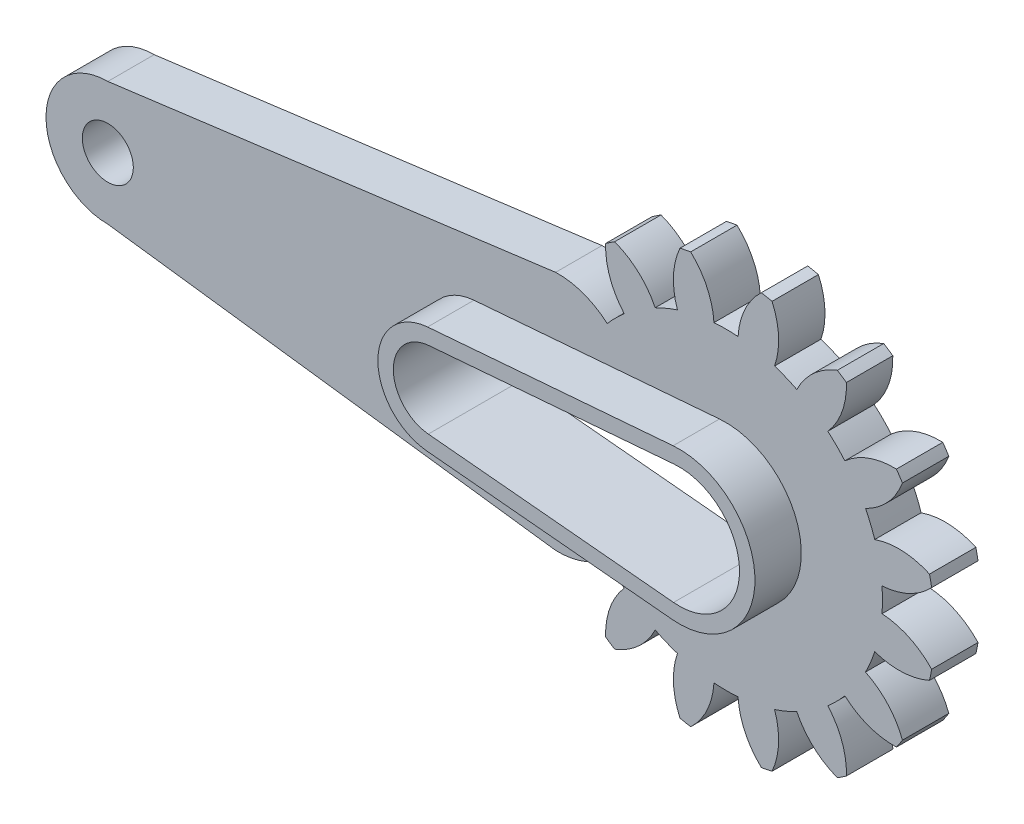
SolidWorks part; units mm, degrees
ref_plane "Front Plane" through (0, 0, 0) normal (0, 0, 1) x (1, 0, 0)
ref_plane "Top Plane" through (0, 0, 0) normal (0, 1, 0) x (1, 0, 0)
ref_plane "Right Plane" through (0, 0, 0) normal (1, 0, 0) x (0, 0, -1)
sketch "Sketch1" plane through (0, 0, 0) normal (0, 0, 1) x (1, 0, 0)
  line L0 (2.5866, 4.9713) -> (-37.4134, 4.9713) construction
  line L7 (2.2444, 8.8475) -> (-13.6422, 7.5599)
  line L8 (-13.6757, 2.5792) -> (2.192, 1.0776)
  line L9 (2.2848, 8.3491) -> (-13.6018, 7.0615)
  line L10 (-13.6286, 3.077) -> (2.2391, 1.5753)
  line L13 (2.1636, 9.8442) -> (-13.723, 8.5566)
  line L14 (-13.77, 1.5836) -> (2.0978, 0.082)
  line L15 (-37.4134, 8.9713) -> (-8.4386, 12.7621)
  line L16 (-37.4134, 0.9713) -> (-8.4386, -2.8194)
  circle A1 centre (2.5866, 4.9713) radius 1.5
  circle A2 centre (2.5866, 4.9713) radius 1.5
  arc A3 (-37.4134, 8.9713) -> (-37.4134, 0.9713) centre (-37.4134, 4.9713) ccw
  circle A4 centre (2.5866, 4.9713) radius 1.5224
  circle A5 centre (2.5866, 4.9713) radius 1.5
  circle A6 centre (2.5866, 4.9713) radius 1.65
  circle A7 centre (-37.4134, 4.9713) radius 1.65
  arc A8 (2.192, 1.0776) -> (2.2444, 8.8475) centre (2.5594, 4.9602) ccw
  arc A9 (-0.8405, 4.9831) -> (2.2391, 1.5753) centre (2.5594, 4.9602) ccw construction
  arc A13 (-0.8405, 4.9831) -> (-0.8406, 4.9713) centre (2.5594, 4.9602) ccw
  arc A16 (-13.6422, 7.5599) -> (-13.6757, 2.5792) centre (-13.4402, 5.0681) ccw
  arc A18 (-0.8405, 4.9831) -> (2.2391, 1.5753) centre (2.5594, 4.9602) ccw
  arc A19 (2.2848, 8.3491) -> (-0.8405, 4.9831) centre (2.5594, 4.9602) ccw
  arc A20 (-13.6018, 7.0615) -> (-13.6286, 3.077) centre (-13.4402, 5.0681) ccw
  arc A21 (-0.8405, 4.9831) -> (-0.8406, 4.9713) centre (2.5594, 4.9602) ccw
  arc A24 (-13.723, 8.5566) -> (-13.77, 1.5836) centre (-13.4402, 5.0681) ccw
  arc A25 (2.0978, 0.082) -> (2.1636, 9.8442) centre (2.5594, 4.9602) ccw
  circle A31 centre (2.5594, 4.9602) radius 3.4
  arc A32 (-0.8405, 4.9831) -> (-0.8406, 4.9713) centre (2.5594, 4.9602) ccw
  arc A66 (12.6806, 5.7512) -> (15.8915, 7.2585) centre (12.3907, 10.5424) ccw
  arc A67 (15.8915, 7.2585) -> (15.754, 7.9499) centre (2.5866, 4.9713) ccw
  arc A68 (15.754, 7.9499) -> (12.2106, 8.1137) centre (13.7763, 3.5762) ccw
  arc A69 (12.2106, 8.1137) -> (11.6138, 9.5546) centre (2.5866, 4.9713) ccw
  arc A70 (11.6138, 9.5546) -> (14.0035, 12.1759) centre (9.5124, 13.8702) ccw
  arc A71 (14.0035, 12.1759) -> (13.6118, 12.7621) centre (2.5866, 4.9713) ccw
  arc A72 (13.6118, 12.7621) -> (10.2755, 11.5574) centre (13.4584, 7.9645) ccw
  arc A73 (10.2755, 11.5574) -> (9.1727, 12.6602) centre (2.5866, 4.9713) ccw
  arc A74 (9.1727, 12.6602) -> (10.3773, 15.9965) centre (5.5798, 15.8432) ccw
  arc A75 (10.3773, 15.9965) -> (9.7912, 16.3882) centre (2.5866, 4.9713) ccw
  arc A76 (9.7912, 16.3882) -> (7.1699, 13.9985) centre (11.4854, 11.8971) ccw
  arc A77 (7.1699, 13.9985) -> (5.729, 14.5953) centre (2.5866, 4.9713) ccw
  arc A78 (5.729, 14.5953) -> (5.5652, 18.1387) centre (1.1915, 16.161) ccw
  arc A79 (5.5652, 18.1387) -> (4.8738, 18.2762) centre (2.5866, 4.9713) ccw
  arc A80 (4.8738, 18.2762) -> (3.3664, 15.0653) centre (8.1577, 14.7754) ccw
  arc A81 (3.3664, 15.0653) -> (1.8068, 15.0653) centre (2.5866, 4.9713) ccw
  arc A82 (1.8068, 15.0653) -> (0.2995, 18.2762) centre (-2.9844, 14.7754) ccw
  arc A83 (0.2995, 18.2762) -> (-0.3919, 18.1387) centre (2.5866, 4.9713) ccw
  arc A84 (-0.3919, 18.1387) -> (-0.5557, 14.5953) centre (3.9818, 16.161) ccw
  arc A85 (-0.5557, 14.5953) -> (-1.9966, 13.9985) centre (2.5866, 4.9713) ccw
  arc A86 (-1.9966, 13.9985) -> (-4.6179, 16.3882) centre (-6.3122, 11.8971) ccw
  arc A87 (-4.6179, 16.3882) -> (-5.2041, 15.9965) centre (2.5866, 4.9713) ccw
  arc A88 (-5.2041, 15.9965) -> (-3.9994, 12.6602) centre (-0.4065, 15.8432) ccw
  arc A89 (-3.9994, 12.6602) -> (-5.1022, 11.5574) centre (2.5866, 4.9713) ccw
  arc A90 (-5.1022, 11.5574) -> (-8.4386, 12.7621) centre (-8.2852, 7.9645) ccw
  arc A91 (-8.4386, 12.7621) -> (-8.8302, 12.1759) centre (2.5866, 4.9713) ccw
  arc A92 (-8.8302, 12.1759) -> (-6.4405, 9.5546) centre (-4.3391, 13.8702) ccw
  arc A93 (-6.4405, 9.5546) -> (-7.0373, 8.1137) centre (2.5866, 4.9713) ccw
  arc A94 (-7.0373, 8.1137) -> (-10.5807, 7.9499) centre (-8.603, 3.5762) ccw
  arc A95 (-10.5807, 7.9499) -> (-10.7182, 7.2585) centre (2.5866, 4.9713) ccw
  arc A96 (-10.7182, 7.2585) -> (-7.5073, 5.7512) centre (-7.2174, 10.5424) ccw
  arc A97 (-7.5073, 5.7512) -> (-7.5073, 4.1915) centre (2.5866, 4.9713) ccw
  arc A98 (-7.5073, 4.1915) -> (-10.7182, 2.6842) centre (-7.2174, -0.5997) ccw
  arc A99 (-10.7182, 2.6842) -> (-10.5807, 1.9928) centre (2.5866, 4.9713) ccw
  arc A100 (-10.5807, 1.9928) -> (-7.0373, 1.829) centre (-8.603, 6.3665) ccw
  arc A101 (-7.0373, 1.829) -> (-6.4405, 0.3881) centre (2.5866, 4.9713) ccw
  arc A102 (-6.4405, 0.3881) -> (-8.8302, -2.2332) centre (-4.3391, -3.9275) ccw
  arc A103 (-8.8302, -2.2332) -> (-8.4386, -2.8194) centre (2.5866, 4.9713) ccw
  arc A104 (-8.4386, -2.8194) -> (-5.1022, -1.6147) centre (-8.2852, 1.9782) ccw
  arc A105 (-5.1022, -1.6147) -> (-3.9994, -2.7175) centre (2.5866, 4.9713) ccw
  arc A106 (-3.9994, -2.7175) -> (-5.2041, -6.0538) centre (-0.4065, -5.9005) ccw
  arc A107 (-5.2041, -6.0538) -> (-4.6179, -6.4455) centre (2.5866, 4.9713) ccw
  arc A108 (-4.6179, -6.4455) -> (-1.9966, -4.0558) centre (-6.3122, -1.9544) ccw
  arc A109 (-1.9966, -4.0558) -> (-0.5557, -4.6526) centre (2.5866, 4.9713) ccw
  arc A110 (-0.5557, -4.6526) -> (-0.3919, -8.196) centre (3.9818, -6.2183) ccw
  arc A111 (-0.3919, -8.196) -> (0.2995, -8.3335) centre (2.5866, 4.9713) ccw
  arc A112 (0.2995, -8.3335) -> (1.8068, -5.1226) centre (-2.9844, -4.8327) ccw
  arc A113 (1.8068, -5.1226) -> (3.3664, -5.1226) centre (2.5866, 4.9713) ccw
  arc A114 (3.3664, -5.1226) -> (4.8738, -8.3335) centre (8.1577, -4.8327) ccw
  arc A115 (4.8738, -8.3335) -> (5.5652, -8.196) centre (2.5866, 4.9713) ccw
  arc A116 (5.5652, -8.196) -> (5.729, -4.6526) centre (1.1915, -6.2183) ccw
  arc A117 (5.729, -4.6526) -> (7.1699, -4.0558) centre (2.5866, 4.9713) ccw
  arc A118 (7.1699, -4.0558) -> (9.7912, -6.4455) centre (11.4854, -1.9544) ccw
  arc A119 (9.7912, -6.4455) -> (10.3773, -6.0538) centre (2.5866, 4.9713) ccw
  arc A120 (10.3773, -6.0538) -> (9.1727, -2.7175) centre (5.5798, -5.9005) ccw
  arc A121 (9.1727, -2.7175) -> (10.2755, -1.6147) centre (2.5866, 4.9713) ccw
  arc A122 (10.2755, -1.6147) -> (13.6118, -2.8194) centre (13.4584, 1.9782) ccw
  arc A123 (13.6118, -2.8194) -> (14.0035, -2.2332) centre (2.5866, 4.9713) ccw
  arc A124 (14.0035, -2.2332) -> (11.6138, 0.3881) centre (9.5124, -3.9275) ccw
  arc A125 (11.6138, 0.3881) -> (12.2106, 1.829) centre (2.5866, 4.9713) ccw
  arc A126 (12.2106, 1.829) -> (15.754, 1.9928) centre (13.7763, 6.3665) ccw
  arc A127 (15.754, 1.9928) -> (15.8915, 2.6842) centre (2.5866, 4.9713) ccw
  arc A128 (15.8915, 2.6842) -> (12.6806, 4.1915) centre (12.3907, -0.5997) ccw
  arc A129 (12.6806, 4.1915) -> (12.6806, 5.7512) centre (2.5866, 4.9713) ccw
  arc A130 (12.6806, 5.7512) -> (15.8915, 7.2585) centre (12.3907, 10.5424) ccw
  arc A131 (15.8915, 7.2585) -> (15.754, 7.9499) centre (2.5866, 4.9713) ccw
  arc A132 (15.754, 7.9499) -> (12.2106, 8.1137) centre (13.7763, 3.5762) ccw
  arc A133 (12.2106, 8.1137) -> (11.6138, 9.5546) centre (2.5866, 4.9713) ccw
  arc A134 (11.6138, 9.5546) -> (14.0035, 12.1759) centre (9.5124, 13.8702) ccw
  arc A135 (14.0035, 12.1759) -> (13.6118, 12.7621) centre (2.5866, 4.9713) ccw
  arc A136 (13.6118, 12.7621) -> (10.2755, 11.5574) centre (13.4584, 7.9645) ccw
  arc A137 (10.2755, 11.5574) -> (9.1727, 12.6602) centre (2.5866, 4.9713) ccw
  arc A138 (9.1727, 12.6602) -> (10.3773, 15.9965) centre (5.5798, 15.8432) ccw
  arc A139 (10.3773, 15.9965) -> (9.7912, 16.3882) centre (2.5866, 4.9713) ccw
  arc A140 (9.7912, 16.3882) -> (7.1699, 13.9985) centre (11.4854, 11.8971) ccw
  arc A141 (7.1699, 13.9985) -> (5.729, 14.5953) centre (2.5866, 4.9713) ccw
  arc A142 (5.729, 14.5953) -> (5.5652, 18.1387) centre (1.1915, 16.161) ccw
  arc A143 (5.5652, 18.1387) -> (4.8738, 18.2762) centre (2.5866, 4.9713) ccw
  arc A144 (4.8738, 18.2762) -> (3.3664, 15.0653) centre (8.1577, 14.7754) ccw
  arc A145 (3.3664, 15.0653) -> (1.8068, 15.0653) centre (2.5866, 4.9713) ccw
  arc A146 (1.8068, 15.0653) -> (0.2995, 18.2762) centre (-2.9844, 14.7754) ccw
  arc A147 (0.2995, 18.2762) -> (-0.3919, 18.1387) centre (2.5866, 4.9713) ccw
  arc A148 (-0.3919, 18.1387) -> (-0.5557, 14.5953) centre (3.9818, 16.161) ccw
  arc A149 (-0.5557, 14.5953) -> (-1.9966, 13.9985) centre (2.5866, 4.9713) ccw
  arc A150 (-1.9966, 13.9985) -> (-4.6179, 16.3882) centre (-6.3122, 11.8971) ccw
  arc A151 (-4.6179, 16.3882) -> (-5.2041, 15.9965) centre (2.5866, 4.9713) ccw
  arc A152 (-5.2041, 15.9965) -> (-3.9994, 12.6602) centre (-0.4065, 15.8432) ccw
  arc A153 (-3.9994, 12.6602) -> (-5.1022, 11.5574) centre (2.5866, 4.9713) ccw
  arc A154 (-5.1022, 11.5574) -> (-8.4386, 12.7621) centre (-8.2852, 7.9645) ccw
  arc A168 (-8.4386, -2.8194) -> (-5.1022, -1.6147) centre (-8.2852, 1.9782) ccw
  arc A169 (-5.1022, -1.6147) -> (-3.9994, -2.7175) centre (2.5866, 4.9713) ccw
  arc A170 (-3.9994, -2.7175) -> (-5.2041, -6.0538) centre (-0.4065, -5.9005) ccw
  arc A171 (-5.2041, -6.0538) -> (-4.6179, -6.4455) centre (2.5866, 4.9713) ccw
  arc A172 (-4.6179, -6.4455) -> (-1.9966, -4.0558) centre (-6.3122, -1.9544) ccw
  arc A173 (-1.9966, -4.0558) -> (-0.5557, -4.6526) centre (2.5866, 4.9713) ccw
  arc A174 (-0.5557, -4.6526) -> (-0.3919, -8.196) centre (3.9818, -6.2183) ccw
  arc A175 (-0.3919, -8.196) -> (0.2995, -8.3335) centre (2.5866, 4.9713) ccw
  arc A176 (0.2995, -8.3335) -> (1.8068, -5.1226) centre (-2.9844, -4.8327) ccw
  arc A177 (1.8068, -5.1226) -> (3.3664, -5.1226) centre (2.5866, 4.9713) ccw
  arc A178 (3.3664, -5.1226) -> (4.8738, -8.3335) centre (8.1577, -4.8327) ccw
  arc A179 (4.8738, -8.3335) -> (5.5652, -8.196) centre (2.5866, 4.9713) ccw
  arc A180 (5.5652, -8.196) -> (5.729, -4.6526) centre (1.1915, -6.2183) ccw
  arc A181 (5.729, -4.6526) -> (7.1699, -4.0558) centre (2.5866, 4.9713) ccw
  arc A182 (7.1699, -4.0558) -> (9.7912, -6.4455) centre (11.4854, -1.9544) ccw
  arc A183 (9.7912, -6.4455) -> (10.3773, -6.0538) centre (2.5866, 4.9713) ccw
  arc A184 (10.3773, -6.0538) -> (9.1727, -2.7175) centre (5.5798, -5.9005) ccw
  arc A185 (9.1727, -2.7175) -> (10.2755, -1.6147) centre (2.5866, 4.9713) ccw
  arc A186 (10.2755, -1.6147) -> (13.6118, -2.8194) centre (13.4584, 1.9782) ccw
  arc A187 (13.6118, -2.8194) -> (14.0035, -2.2332) centre (2.5866, 4.9713) ccw
  arc A188 (14.0035, -2.2332) -> (11.6138, 0.3881) centre (9.5124, -3.9275) ccw
  arc A189 (11.6138, 0.3881) -> (12.2106, 1.829) centre (2.5866, 4.9713) ccw
  arc A190 (12.2106, 1.829) -> (15.754, 1.9928) centre (13.7763, 6.3665) ccw
  arc A191 (15.754, 1.9928) -> (15.8915, 2.6842) centre (2.5866, 4.9713) ccw
  arc A192 (15.8915, 2.6842) -> (12.6806, 4.1915) centre (12.3907, -0.5997) ccw
  arc A193 (12.6806, 4.1915) -> (12.6806, 5.7512) centre (2.5866, 4.9713) ccw
  point P0 (-17.4134, 4.9713)
  dimension "D4" = 3.3
  dimension "D5" = 3.3
  dimension "D3" = 40
  dimension "D6" = 0
  dimension "D7" = 0
  dimension "D1" = 0
  dimension "D8" = 0
  dimension "D9" = 1
extrude "Boss-Extrude1" add sketch "Sketch1" against normal blind 3 contours A154 A153 A152 A151 A150 A149 A148 A147 A146 A145 | A192 A193 A130 A131 A132 A133 A134 A135 A136 A137 A138 A139 A140 A141 A142 A143 A144 A145 A146 A147 A148 A149 A150 A151 A152 A153 A154 A168 A169 A170 A171 A172 A173 A174 A175 A176 A177 A178 | A3 | A16 L7 A8 L8 A24 L14 A25 L13 region at (-4.2007, 8.5316, 0) region at (-12.138, 7.814, 0) region at (-6.2169, 9.1868, 0) region at (-23.8675, 4.9533, 0)
extrude "Boss-Extrude2" add sketch "Sketch1<3>" along normal blind 3 contours A16 L7 A8 L8 A24 L14 A25 L13 region at (-4.2007, 8.5316, 0) region at (-12.138, 7.814, 0)
sketch "Sketch1<3>" plane through (0, 0, 0) normal (0, 0, 1) x (1, 0, 0) same geometry as "Sketch1"
